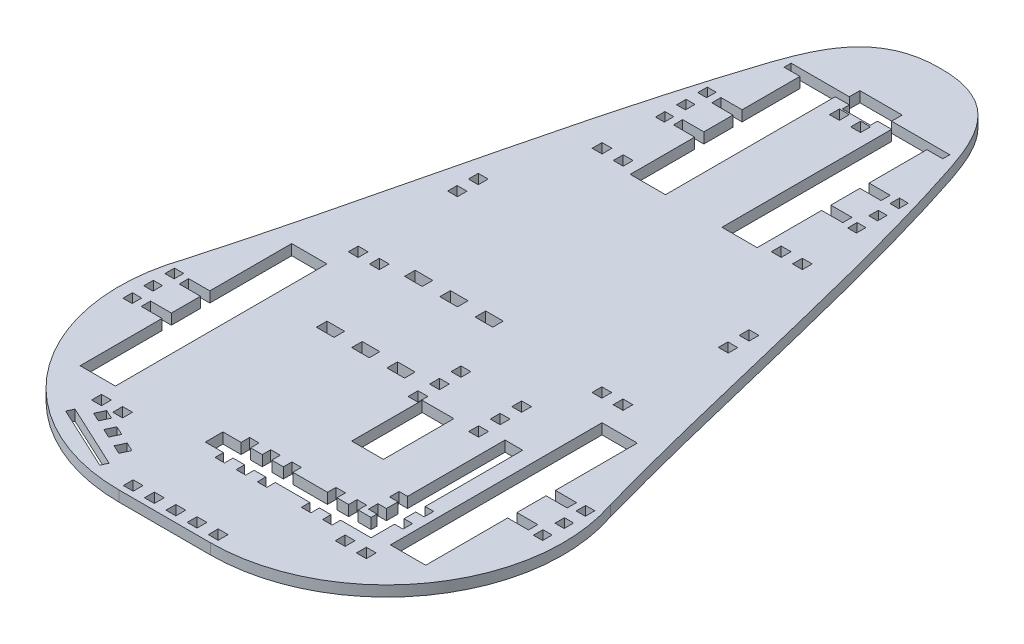
SolidWorks part; units mm, degrees
ref_plane "Front Plane" through (0, 0, 0) normal (0, 0, 1) x (1, 0, 0)
ref_plane "Top Plane" through (0, 0, 0) normal (0, 1, 0) x (1, 0, 0)
ref_plane "Right Plane" through (0, 0, 0) normal (1, 0, 0) x (0, 0, -1)
sketch "Sketch1" plane through (0, 0, 0) normal (0, 1, 0) x (1, 0, 0)
  line L0 (54.872, 210.7624) -> (54.872, -9.2376) construction
  line L1 (41.9035, -9.2376) -> (67.8405, -9.2376)
  line L6 (5.872, 75.7624) -> (15.872, 75.7624)
  line L7 (54.872, -9.2376) -> (64.872, -9.2376)
  line L8 (54.872, -9.2376) -> (44.872, -9.2376)
  line L9 (5.872, 75.7624) -> (5.872, 15.7624)
  line L10 (5.872, 15.7624) -> (15.872, 15.7624)
  line L11 (15.872, 75.7624) -> (15.872, 15.7624)
  line L12 (5.872, 75.7624) -> (15.872, 15.7624) construction
  line L13 (5.872, 15.7624) -> (15.872, 75.7624) construction
  line L18 (-0.128, 52.5374) -> (5.872, 52.5374)
  line L19 (-0.128, 52.5374) -> (-0.128, 49.8874)
  line L35 (103.872, 15.7624) -> (93.872, 15.7624)
  line L36 (93.872, 75.7624) -> (93.872, 15.7624)
  line L37 (103.872, 75.7624) -> (93.872, 75.7624)
  line L38 (103.872, 75.7624) -> (103.872, 15.7624)
  line L40 (36.872, 190.7624) -> (46.872, 190.7624)
  line L41 (36.872, 190.7624) -> (36.872, 140.7624)
  line L42 (36.872, 140.7624) -> (46.872, 140.7624)
  line L43 (46.872, 190.7624) -> (46.872, 140.7624)
  line L44 (36.872, 190.7624) -> (46.872, 140.7624) construction
  line L45 (36.872, 140.7624) -> (46.872, 190.7624) construction
  line L46 (10.872, 45.7624) -> (-10.2667, 45.7624) construction
  line L63 (72.872, 140.7624) -> (62.872, 140.7624)
  line L64 (62.872, 190.7624) -> (62.872, 140.7624)
  line L65 (72.872, 190.7624) -> (62.872, 190.7624)
  line L66 (72.872, 190.7624) -> (72.872, 140.7624)
  line L78 (114.472, 47.1124) -> (111.872, 44.4124) construction
  line L79 (114.472, 44.4124) -> (111.872, 47.1124) construction
  line L80 (114.472, 50.4124) -> (111.872, 53.1124) construction
  line L81 (114.472, 53.1124) -> (111.872, 50.4124) construction
  line L82 (109.7728, 38.9874) -> (103.7728, 41.6374) construction
  line L83 (109.7728, 41.6374) -> (103.7728, 38.9874) construction
  line L84 (109.872, 49.8874) -> (103.872, 52.5374) construction
  line L85 (109.872, 52.5374) -> (103.872, 49.8874) construction
  line L86 (111.7728, 41.1124) -> (111.7728, 38.4124)
  line L87 (114.3728, 38.4124) -> (111.7728, 38.4124)
  line L88 (114.3728, 41.1124) -> (114.3728, 38.4124)
  line L89 (111.872, 44.4124) -> (111.872, 47.1124)
  line L90 (114.472, 47.1124) -> (111.872, 47.1124)
  line L91 (114.472, 44.4124) -> (114.472, 47.1124)
  line L92 (41.872, 165.7624) -> (24.9145, 165.7624) construction
  line L93 (30.872, 172.4874) -> (36.872, 172.4874)
  line L94 (30.872, 172.4874) -> (30.872, 169.8874)
  line L95 (30.872, 169.8874) -> (36.872, 169.8874)
  line L96 (36.872, 172.4874) -> (36.872, 169.8874)
  line L97 (30.872, 172.4874) -> (36.872, 169.8874) construction
  line L98 (30.872, 169.8874) -> (36.872, 172.4874) construction
  line L103 (26.372, 161.1124) -> (28.872, 161.1124)
  line L104 (26.372, 173.1124) -> (28.872, 173.1124)
  line L105 (30.872, 161.6374) -> (36.872, 161.6374)
  line L106 (30.872, 161.6374) -> (30.872, 159.0374)
  line L107 (30.872, 159.0374) -> (36.872, 159.0374)
  line L108 (36.872, 161.6374) -> (36.872, 159.0374)
  line L109 (30.872, 161.6374) -> (36.872, 159.0374) construction
  line L110 (30.872, 159.0374) -> (36.872, 161.6374) construction
  line L111 (26.372, 173.1124) -> (26.372, 170.4124)
  line L112 (26.372, 170.4124) -> (28.872, 170.4124)
  line L113 (28.872, 173.1124) -> (28.872, 170.4124)
  line L114 (26.372, 173.1124) -> (28.872, 170.4124) construction
  line L115 (26.372, 170.4124) -> (28.872, 173.1124) construction
  line L116 (26.372, 164.4124) -> (28.872, 164.4124)
  line L117 (26.372, 164.4124) -> (26.372, 167.1124)
  line L118 (26.372, 167.1124) -> (28.872, 167.1124)
  line L119 (28.872, 164.4124) -> (28.872, 167.1124)
  line L120 (26.372, 164.4124) -> (28.872, 167.1124) construction
  line L121 (26.372, 167.1124) -> (28.872, 164.4124) construction
  line L122 (26.372, 161.1124) -> (26.372, 158.4124)
  line L123 (26.372, 158.4124) -> (28.872, 158.4124)
  line L124 (28.872, 161.1124) -> (28.872, 158.4124)
  line L125 (83.372, 167.1124) -> (80.872, 164.4124) construction
  line L126 (83.372, 164.4124) -> (80.872, 167.1124) construction
  line L127 (83.372, 170.4124) -> (80.872, 173.1124) construction
  line L128 (83.372, 173.1124) -> (80.872, 170.4124) construction
  line L129 (78.872, 159.0374) -> (72.872, 161.6374) construction
  line L130 (78.872, 161.6374) -> (72.872, 159.0374) construction
  line L131 (78.872, 169.8874) -> (72.872, 172.4874) construction
  line L132 (78.872, 172.4874) -> (72.872, 169.8874) construction
  line L133 (80.872, 161.1124) -> (80.872, 158.4124)
  line L134 (83.372, 158.4124) -> (80.872, 158.4124)
  line L135 (83.372, 161.1124) -> (83.372, 158.4124)
  line L136 (80.872, 164.4124) -> (80.872, 167.1124)
  line L137 (83.372, 167.1124) -> (80.872, 167.1124)
  line L138 (83.372, 164.4124) -> (83.372, 167.1124)
  line L139 (83.372, 164.4124) -> (80.872, 164.4124)
  line L140 (80.872, 173.1124) -> (80.872, 170.4124)
  line L141 (83.372, 170.4124) -> (80.872, 170.4124)
  line L142 (83.372, 173.1124) -> (83.372, 170.4124)
  line L143 (72.872, 161.6374) -> (72.872, 159.0374)
  line L144 (78.872, 159.0374) -> (72.872, 159.0374)
  line L145 (78.872, 161.6374) -> (78.872, 159.0374)
  line L146 (78.872, 161.6374) -> (72.872, 161.6374)
  line L147 (83.372, 173.1124) -> (80.872, 173.1124)
  line L148 (83.372, 161.1124) -> (80.872, 161.1124)
  line L149 (72.872, 172.4874) -> (72.872, 169.8874)
  line L150 (78.872, 169.8874) -> (72.872, 169.8874)
  line L151 (78.872, 172.4874) -> (78.872, 169.8874)
  line L152 (78.872, 172.4874) -> (72.872, 172.4874)
  line L153 (-0.128, 49.8874) -> (5.872, 49.8874)
  line L154 (5.872, 52.5374) -> (5.872, 49.8874)
  line L155 (-0.128, 52.5374) -> (5.872, 49.8874) construction
  line L156 (-0.128, 49.8874) -> (5.872, 52.5374) construction
  line L157 (-4.6289, 41.1124) -> (-2.0289, 41.1124)
  line L158 (-4.728, 53.1124) -> (-2.128, 53.1124)
  line L159 (-0.0289, 41.6374) -> (5.9711, 41.6374)
  line L160 (-0.0289, 41.6374) -> (-0.0289, 38.9874)
  line L161 (-0.0289, 38.9874) -> (5.9711, 38.9874)
  line L162 (5.9711, 41.6374) -> (5.9711, 38.9874)
  line L163 (-0.0289, 41.6374) -> (5.9711, 38.9874) construction
  line L164 (-0.0289, 38.9874) -> (5.9711, 41.6374) construction
  line L165 (-4.728, 53.1124) -> (-4.728, 50.4124)
  line L166 (-4.728, 50.4124) -> (-2.128, 50.4124)
  line L167 (-2.128, 53.1124) -> (-2.128, 50.4124)
  line L168 (-4.728, 53.1124) -> (-2.128, 50.4124) construction
  line L169 (-4.728, 50.4124) -> (-2.128, 53.1124) construction
  line L170 (-4.728, 44.4124) -> (-2.128, 44.4124)
  line L171 (-4.728, 44.4124) -> (-4.728, 47.1124)
  line L172 (-4.728, 47.1124) -> (-2.128, 47.1124)
  line L173 (-2.128, 44.4124) -> (-2.128, 47.1124)
  line L174 (-4.728, 44.4124) -> (-2.128, 47.1124) construction
  line L175 (-4.728, 47.1124) -> (-2.128, 44.4124) construction
  line L176 (-4.6289, 41.1124) -> (-4.6289, 38.4124)
  line L177 (-4.6289, 38.4124) -> (-2.0289, 38.4124)
  line L178 (-2.0289, 41.1124) -> (-2.0289, 38.4124)
  line L179 (114.472, 44.4124) -> (111.872, 44.4124)
  line L180 (111.872, 53.1124) -> (111.872, 50.4124)
  line L181 (114.472, 50.4124) -> (111.872, 50.4124)
  line L182 (114.472, 53.1124) -> (114.472, 50.4124)
  line L183 (103.7728, 41.6374) -> (103.7728, 38.9874)
  line L184 (109.7728, 38.9874) -> (103.7728, 38.9874)
  line L185 (109.7728, 41.6374) -> (109.7728, 38.9874)
  line L186 (109.7728, 41.6374) -> (103.7728, 41.6374)
  line L187 (114.472, 53.1124) -> (111.872, 53.1124)
  line L188 (114.3728, 41.1124) -> (111.7728, 41.1124)
  line L189 (103.872, 52.5374) -> (103.872, 49.8874)
  line L190 (109.872, 49.8874) -> (103.872, 49.8874)
  line L191 (109.872, 52.5374) -> (109.872, 49.8874)
  line L192 (109.872, 52.5374) -> (103.872, 52.5374)
  line L193 (103.872, 45.7624) -> (5.872, 45.7624) construction
  line L200 (62.872, 55.7624) -> (71.872, 55.7624)
  line L201 (62.872, 55.7624) -> (62.872, 35.7624)
  line L202 (62.872, 35.7624) -> (71.872, 35.7624)
  line L203 (71.872, 55.7624) -> (71.872, 35.7624)
  line L204 (62.872, 55.7624) -> (71.872, 35.7624) construction
  line L205 (62.872, 35.7624) -> (71.872, 55.7624) construction
  line L211 (39.9211, 61.7172) -> (44.9211, 61.7172)
  line L213 (59.9211, 69.7172) -> (62.7211, 69.7172)
  line L214 (59.9211, 57.5172) -> (62.7211, 57.5172)
  line L215 (59.9211, 57.5172) -> (59.9211, 54.7172)
  line L216 (59.9211, 54.7172) -> (62.7211, 54.7172)
  line L217 (62.7211, 57.5172) -> (62.7211, 54.7172)
  line L218 (59.9211, 57.5172) -> (62.7211, 54.7172) construction
  line L219 (59.9211, 54.7172) -> (62.7211, 57.5172) construction
  line L220 (59.9211, 69.7172) -> (59.9211, 66.9172)
  line L221 (59.9211, 66.9172) -> (62.7211, 66.9172)
  line L222 (62.7211, 69.7172) -> (62.7211, 66.9172)
  line L223 (59.9211, 63.6172) -> (62.7211, 63.6172)
  line L224 (59.9211, 63.6172) -> (59.9211, 60.8172)
  line L225 (59.9211, 60.8172) -> (62.7211, 60.8172)
  line L226 (62.7211, 63.6172) -> (62.7211, 60.8172)
  line L227 (77.1211, 69.7172) -> (79.9211, 69.7172)
  line L228 (77.1211, 57.5172) -> (79.9211, 57.5172)
  line L229 (77.1211, 57.5172) -> (77.1211, 54.7172)
  line L230 (77.1211, 54.7172) -> (79.9211, 54.7172)
  line L231 (79.9211, 57.5172) -> (79.9211, 54.7172)
  line L232 (77.1211, 69.7172) -> (77.1211, 66.9172)
  line L233 (77.1211, 66.9172) -> (79.9211, 66.9172)
  line L234 (79.9211, 69.7172) -> (79.9211, 66.9172)
  line L235 (77.1211, 63.6172) -> (79.9211, 63.6172)
  line L236 (77.1211, 63.6172) -> (77.1211, 60.8172)
  line L237 (77.1211, 60.8172) -> (79.9211, 60.8172)
  line L238 (79.9211, 63.6172) -> (79.9211, 60.8172)
  line L244 (49.9211, 61.7172) -> (54.9211, 61.7172)
  line L245 (49.9211, 61.7172) -> (49.9211, 58.7172)
  line L246 (49.9211, 58.7172) -> (54.9211, 58.7172)
  line L247 (54.9211, 61.7172) -> (54.9211, 58.7172)
  line L248 (49.9211, 61.7172) -> (54.9211, 58.7172) construction
  line L249 (49.9211, 58.7172) -> (54.9211, 61.7172) construction
  line L250 (39.9211, 61.7172) -> (39.9211, 58.7172)
  line L251 (39.9211, 58.7172) -> (44.9211, 58.7172)
  line L252 (44.9211, 61.7172) -> (44.9211, 58.7172)
  line L253 (29.9211, 61.7172) -> (34.9211, 61.7172)
  line L254 (29.9211, 61.7172) -> (29.9211, 58.7172)
  line L255 (29.9211, 58.7172) -> (34.9211, 58.7172)
  line L256 (34.9211, 61.7172) -> (34.9211, 58.7172)
  line L257 (49.9211, 86.7172) -> (54.9211, 86.7172)
  line L258 (49.9211, 86.7172) -> (49.9211, 83.7172)
  line L259 (49.9211, 83.7172) -> (54.9211, 83.7172)
  line L260 (54.9211, 86.7172) -> (54.9211, 83.7172)
  line L261 (39.9211, 86.7172) -> (44.9211, 86.7172)
  line L262 (39.9211, 86.7172) -> (39.9211, 83.7172)
  line L263 (39.9211, 83.7172) -> (44.9211, 83.7172)
  line L264 (44.9211, 86.7172) -> (44.9211, 83.7172)
  line L265 (29.9211, 86.7172) -> (34.9211, 86.7172)
  line L266 (29.9211, 86.7172) -> (29.9211, 83.7172)
  line L267 (29.9211, 83.7172) -> (34.9211, 83.7172)
  line L268 (34.9211, 86.7172) -> (34.9211, 83.7172)
  line L279 (15.072, 113.4624) -> (17.872, 113.4624)
  line L284 (15.0729, 119.4624) -> (17.8729, 119.4624)
  line L285 (15.0729, 119.4624) -> (15.0729, 116.6624)
  line L286 (15.0729, 116.6624) -> (17.8729, 116.6624)
  line L287 (17.8729, 119.4624) -> (17.8729, 116.6624)
  line L288 (15.072, 113.4624) -> (15.072, 110.7624)
  line L289 (15.072, 110.7624) -> (17.872, 110.7624)
  line L290 (17.872, 113.4624) -> (17.872, 110.7624)
  line L291 (287.5426, 108.3221) -> (290.3426, 108.3221)
  line L292 (212.3426, 111.3221) -> (290.3426, 111.3221)
  line L293 (212.3426, 111.3221) -> (212.3426, 29.7221)
  line L294 (212.3426, 29.7221) -> (290.3426, 29.7221)
  line L295 (290.3426, 111.3221) -> (290.3426, 29.7221)
  line L296 (212.3426, 108.3221) -> (215.1426, 108.3221)
  line L297 (212.3426, 108.3221) -> (212.3426, 105.5221)
  line L298 (212.3426, 105.5221) -> (215.1426, 105.5221)
  line L299 (215.1426, 108.3221) -> (215.1426, 105.5221)
  line L300 (287.5426, 108.3221) -> (287.5426, 105.5221)
  line L301 (287.5426, 105.5221) -> (290.3426, 105.5221)
  line L302 (290.3426, 108.3221) -> (290.3426, 105.5221)
  line L303 (218.3426, 108.3221) -> (221.1426, 108.3221)
  line L304 (218.3426, 108.3221) -> (218.3426, 105.5221)
  line L305 (218.3426, 105.5221) -> (221.1426, 105.5221)
  line L306 (221.1426, 108.3221) -> (221.1426, 105.5221)
  line L307 (281.5426, 84.5298) -> (284.3426, 84.5298)
  line L308 (281.5426, 84.5298) -> (281.5426, 81.7298)
  line L309 (281.5426, 81.7298) -> (284.3426, 81.7298)
  line L310 (284.3426, 84.5298) -> (284.3426, 81.7298)
  line L311 (287.5426, 35.5221) -> (290.3426, 35.5221)
  line L312 (212.3426, 35.5221) -> (215.1426, 35.5221)
  line L313 (212.3426, 35.5221) -> (212.3426, 32.7221)
  line L314 (212.3426, 32.7221) -> (215.1426, 32.7221)
  line L315 (215.1426, 35.5221) -> (215.1426, 32.7221)
  line L316 (287.5426, 35.5221) -> (287.5426, 32.7221)
  line L317 (287.5426, 32.7221) -> (290.3426, 32.7221)
  line L318 (290.3426, 35.5221) -> (290.3426, 32.7221)
  line L319 (218.3426, 35.5221) -> (221.1426, 35.5221)
  line L320 (218.3426, 35.5221) -> (218.3426, 32.7221)
  line L321 (218.3426, 32.7221) -> (221.1426, 32.7221)
  line L322 (221.1426, 35.5221) -> (221.1426, 32.7221)
  line L323 (281.5426, 35.5221) -> (284.3426, 35.5221)
  line L324 (281.5426, 35.5221) -> (281.5426, 32.7221)
  line L325 (281.5426, 32.7221) -> (284.3426, 32.7221)
  line L326 (284.3426, 35.5221) -> (284.3426, 32.7221)
  line L332 (15.9201, 84.5624) -> (18.7201, 84.5624)
  line L333 (15.9201, 84.5624) -> (15.9201, 81.7624)
  line L334 (15.9201, 81.7624) -> (18.7201, 81.7624)
  line L335 (18.7201, 84.5624) -> (18.7201, 81.7624)
  line L339 (21.9201, 84.5624) -> (24.7201, 84.5624)
  line L340 (21.9201, 84.5624) -> (21.9201, 81.7624)
  line L341 (21.9201, 81.7624) -> (24.7201, 81.7624)
  line L342 (24.7201, 84.5624) -> (24.7201, 81.7624)
  line L348 (15.9201, 11.7624) -> (18.7201, 11.7624)
  line L349 (15.9201, 11.7624) -> (15.9201, 8.9624)
  line L350 (15.9201, 8.9624) -> (18.7201, 8.9624)
  line L351 (18.7201, 11.7624) -> (18.7201, 8.9624)
  line L355 (21.9201, 11.7624) -> (24.7201, 11.7624)
  line L356 (21.9201, 11.7624) -> (21.9201, 8.9624)
  line L357 (21.9201, 8.9624) -> (24.7201, 8.9624)
  line L358 (24.7201, 11.7624) -> (24.7201, 8.9624)
  line L363 (25.072, 144.5629) -> (27.872, 144.5629)
  line L368 (25.072, 144.5629) -> (25.072, 141.7629)
  line L369 (25.072, 141.7629) -> (27.872, 141.7629)
  line L370 (27.872, 144.5629) -> (27.872, 141.7629)
  line L371 (31.072, 144.5624) -> (33.872, 144.5624)
  line L372 (31.072, 144.5624) -> (31.072, 141.7624)
  line L373 (31.072, 141.7624) -> (33.872, 141.7624)
  line L374 (33.872, 144.5624) -> (33.872, 141.7624)
  line L375 (75.872, 144.5624) -> (75.872, 141.7624)
  line L376 (78.672, 141.7624) -> (75.872, 141.7624)
  line L377 (78.672, 144.5624) -> (78.672, 141.7624)
  line L378 (78.672, 144.5624) -> (75.872, 144.5624)
  line L379 (81.872, 144.5629) -> (81.872, 141.7629)
  line L380 (84.672, 141.7629) -> (81.872, 141.7629)
  line L381 (84.672, 144.5629) -> (84.672, 141.7629)
  line L382 (84.672, 144.5629) -> (81.872, 144.5629)
  line L383 (50.4739, 186.4794) -> (50.472, 183.6794)
  line L384 (32.372, 190.884) -> (77.372, 190.884)
  line L385 (32.372, 190.884) -> (32.372, 188.884)
  line L386 (32.372, 188.884) -> (77.372, 188.884)
  line L387 (77.372, 190.884) -> (77.372, 188.884)
  line L388 (48.872, 193.884) -> (60.872, 193.884)
  line L389 (48.872, 193.884) -> (48.872, 190.884)
  line L390 (48.872, 190.884) -> (60.872, 190.884)
  line L391 (60.872, 193.884) -> (60.872, 190.884)
  line L392 (53.272, 183.6794) -> (50.472, 183.6794)
  line L393 (53.272, 186.4794) -> (53.272, 183.6794)
  line L394 (53.272, 186.4794) -> (50.4739, 186.4794)
  line L404 (85.372, 55.7624) -> (88.372, 55.7624)
  line L405 (85.372, 55.7624) -> (85.372, 15.7624)
  line L406 (85.372, 15.7624) -> (88.372, 15.7624)
  line L407 (88.372, 55.7624) -> (88.372, 15.7624)
  line L408 (44.372, 18.7624) -> (88.372, 18.7624)
  line L409 (44.372, 18.7624) -> (44.372, 15.7624)
  line L410 (44.372, 15.7624) -> (88.372, 15.7624)
  line L411 (88.372, 18.7624) -> (88.372, 15.7624)
  line L471 (41.9035, -9.2376) -> (64.872, -9.2376)
  line L480 (47.522, 22.1624) -> (47.522, 19.7624)
  line L481 (50.222, 19.7624) -> (47.522, 19.7624)
  line L482 (50.222, 22.1624) -> (50.222, 19.7624)
  line L483 (50.222, 22.1624) -> (47.522, 22.1624)
  line L484 (53.522, 22.1624) -> (53.522, 19.7624)
  line L485 (56.222, 19.7624) -> (53.522, 19.7624)
  line L486 (56.222, 22.1624) -> (56.222, 19.7624)
  line L487 (56.222, 22.1624) -> (53.522, 22.1624)
  line L488 (59.522, 22.1624) -> (59.522, 19.7624)
  line L489 (62.222, 19.7624) -> (59.522, 19.7624)
  line L490 (62.222, 22.1624) -> (62.222, 19.7624)
  line L491 (62.222, 22.1624) -> (59.522, 22.1624)
  line L492 (56.472, 186.4794) -> (59.2701, 186.4794)
  line L493 (56.472, 186.4794) -> (56.472, 183.6794)
  line L494 (56.472, 183.6794) -> (59.272, 183.6794)
  line L495 (59.2701, 186.4794) -> (59.272, 183.6794)
  line L496 (94.672, 113.4624) -> (94.672, 110.7624)
  line L497 (94.672, 110.7624) -> (91.872, 110.7624)
  line L498 (91.872, 113.4624) -> (91.872, 110.7624)
  line L499 (94.672, 113.4624) -> (91.872, 113.4624)
  line L500 (94.671, 119.4624) -> (94.671, 116.6624)
  line L501 (94.671, 116.6624) -> (91.871, 116.6624)
  line L502 (91.871, 119.4624) -> (91.871, 116.6624)
  line L503 (94.671, 119.4624) -> (91.871, 119.4624)
  line L504 (87.8238, 11.7624) -> (87.8238, 8.9624)
  line L505 (87.8238, 8.9624) -> (85.0238, 8.9624)
  line L506 (85.0238, 11.7624) -> (85.0238, 8.9624)
  line L507 (87.8238, 11.7624) -> (85.0238, 11.7624)
  line L508 (93.8238, 11.7624) -> (93.8238, 8.9624)
  line L509 (93.8238, 8.9624) -> (91.0238, 8.9624)
  line L510 (91.0238, 11.7624) -> (91.0238, 8.9624)
  line L511 (93.8238, 11.7624) -> (91.0238, 11.7624)
  line L512 (87.8238, 84.5624) -> (87.8238, 81.7624)
  line L513 (87.8238, 81.7624) -> (85.0238, 81.7624)
  line L514 (85.0238, 84.5624) -> (85.0238, 81.7624)
  line L515 (87.8238, 84.5624) -> (85.0238, 84.5624)
  line L516 (93.8238, 84.5624) -> (93.8238, 81.7624)
  line L517 (93.8238, 81.7624) -> (91.0238, 81.7624)
  line L518 (91.0238, 84.5624) -> (91.0238, 81.7624)
  line L519 (93.8238, 84.5624) -> (91.0238, 84.5624)
  line L520 (76.372, 18.7624) -> (76.372, 15.7624) construction
  line L521 (64.372, 18.7624) -> (88.372, 18.7624)
  line L522 (64.372, 18.7624) -> (64.372, 15.7624)
  line L523 (64.372, 15.7624) -> (88.372, 15.7624)
  line L524 (88.372, 18.7624) -> (88.372, 15.7624)
  line L525 (76.372, 27.5136) -> (76.372, 8.1564) construction
  line L526 (85.372, 25.7624) -> (88.372, 25.7624) construction
  line L527 (85.372, 35.7624) -> (88.372, 35.7624)
  line L528 (85.372, 35.7624) -> (85.372, 15.7624)
  line L529 (85.372, 15.7624) -> (88.372, 15.7624)
  line L530 (88.372, 35.7624) -> (88.372, 15.7624)
  line L531 (91.4767, 25.7624) -> (69.6189, 25.7624) construction
  line L532 (44.372, 17.2624) -> (64.372, 17.2624) construction
  line L537 (84.372, 57.7624) -> (89.372, 57.7624)
  line L538 (84.372, 57.7624) -> (84.372, 14.7624)
  line L539 (84.372, 14.7624) -> (89.372, 14.7624)
  line L540 (89.372, 57.7624) -> (89.372, 14.7624)
  line L541 (42.372, 19.7624) -> (89.372, 19.7624)
  line L542 (42.372, 19.7624) -> (42.372, 14.7624)
  line L543 (42.372, 14.7624) -> (89.372, 14.7624)
  line L544 (89.372, 19.7624) -> (89.372, 14.7624)
  line L545 (74.722, 14.7624) -> (74.722, 12.3624)
  line L546 (74.722, 12.3624) -> (72.022, 12.3624)
  line L547 (72.022, 14.7624) -> (72.022, 12.3624)
  line L548 (74.722, 14.7624) -> (72.022, 14.7624)
  line L553 (80.722, 14.7624) -> (80.722, 12.3624)
  line L554 (78.022, 14.7624) -> (80.722, 14.7624)
  line L555 (78.022, 14.7624) -> (78.022, 12.3624)
  line L556 (78.022, 12.3624) -> (80.722, 12.3624)
  line L557 (64.372, 17.2624) -> (88.372, 17.2624) construction
  line L558 (78.022, 19.7624) -> (80.722, 19.7624)
  line L559 (78.022, 19.7624) -> (78.022, 22.1624)
  line L560 (78.022, 22.1624) -> (80.722, 22.1624)
  line L561 (80.722, 19.7624) -> (80.722, 22.1624)
  line L562 (72.022, 19.7624) -> (72.022, 22.1624)
  line L563 (74.722, 19.7624) -> (72.022, 19.7624)
  line L564 (74.722, 19.7624) -> (74.722, 22.1624)
  line L565 (74.722, 22.1624) -> (72.022, 22.1624)
  line L566 (81.972, 27.4124) -> (84.372, 27.4124)
  line L567 (81.972, 27.4124) -> (81.972, 30.1124)
  line L568 (81.972, 30.1124) -> (84.372, 30.1124)
  line L569 (84.372, 27.4124) -> (84.372, 30.1124)
  line L574 (86.872, 35.7624) -> (86.872, 15.7624) construction
  line L575 (81.972, 24.1124) -> (81.972, 21.4124)
  line L576 (81.972, 21.4124) -> (84.372, 21.4124)
  line L577 (84.372, 24.1124) -> (84.372, 21.4124)
  line L578 (81.972, 24.1124) -> (84.372, 24.1124)
  line L579 (91.772, 24.1124) -> (89.372, 24.1124)
  line L580 (89.372, 24.1124) -> (89.372, 21.4124)
  line L581 (91.772, 21.4124) -> (89.372, 21.4124)
  line L582 (91.772, 24.1124) -> (91.772, 21.4124)
  line L583 (91.772, 27.4124) -> (91.772, 30.1124)
  line L584 (91.772, 30.1124) -> (89.372, 30.1124)
  line L585 (89.372, 27.4124) -> (89.372, 30.1124)
  line L586 (91.772, 27.4124) -> (89.372, 27.4124)
  line L588 (50.872, 188.884) -> (58.872, 188.884)
  line L589 (50.872, 188.884) -> (50.872, 186.884)
  line L590 (50.872, 186.884) -> (58.872, 186.884)
  line L591 (58.872, 188.884) -> (58.872, 186.884)
  line L659 (24.863, 0.1599) -> (24.0178, -1.6527) construction
  line L660 (59.522, -4.7376) -> (62.322, -4.7376)
  line L661 (53.522, -4.7376) -> (56.322, -4.7376)
  line L662 (53.522, -4.7376) -> (53.522, -7.5376)
  line L663 (53.522, -7.5376) -> (56.322, -7.5376)
  line L664 (56.322, -4.7376) -> (56.322, -7.5376)
  line L665 (59.522, -4.7376) -> (59.522, -7.5376)
  line L666 (59.522, -7.5376) -> (62.322, -7.5376)
  line L667 (62.322, -4.7376) -> (62.322, -7.5376)
  line L668 (65.522, -4.7376) -> (68.322, -4.7376)
  line L669 (65.522, -4.7376) -> (65.522, -7.5376)
  line L670 (65.522, -7.5376) -> (68.322, -7.5376)
  line L671 (68.322, -4.7376) -> (68.322, -7.5376)
  line L672 (44.222, -4.7376) -> (44.222, -7.5376)
  line L673 (44.222, -7.5376) -> (41.422, -7.5376)
  line L674 (41.422, -4.7376) -> (41.422, -7.5376)
  line L675 (44.222, -4.7376) -> (41.422, -4.7376)
  line L676 (50.222, -4.7376) -> (50.222, -7.5376)
  line L677 (50.222, -7.5376) -> (47.422, -7.5376)
  line L678 (47.422, -4.7376) -> (47.422, -7.5376)
  line L679 (50.222, -4.7376) -> (47.422, -4.7376)
  line L689 (20.6529, 8.5227) -> (19.4695, 5.9851)
  line L690 (22.0072, 4.8017) -> (19.4695, 5.9851)
  line L691 (14.9547, 2.5735) -> (33.0809, -5.8789)
  line L692 (14.9547, 2.5735) -> (15.8, 4.3861)
  line L693 (15.8, 4.3861) -> (33.9261, -4.0663)
  line L694 (33.0809, -5.8789) -> (33.9261, -4.0663)
  line L698 (23.1905, 7.3394) -> (22.0072, 4.8017)
  line L699 (23.1905, 7.3394) -> (20.6529, 8.5227)
  line L700 (26.0907, 5.987) -> (24.9074, 3.4493)
  line L701 (27.445, 2.266) -> (24.9074, 3.4493)
  line L702 (28.6284, 4.8037) -> (27.445, 2.266)
  line L703 (28.6284, 4.8037) -> (26.0907, 5.987)
  line L704 (31.5286, 3.4513) -> (30.3452, 0.9136)
  line L705 (32.8829, -0.2697) -> (30.3452, 0.9136)
  line L706 (34.0662, 2.268) -> (32.8829, -0.2697)
  line L707 (34.0662, 2.268) -> (31.5286, 3.4513)
  line L708 (62.222, 12.3624) -> (59.522, 12.3624)
  line L709 (62.222, 12.3624) -> (62.222, 14.7624)
  line L710 (62.222, 14.7624) -> (59.522, 14.7624)
  line L711 (59.522, 12.3624) -> (59.522, 14.7624)
  line L712 (56.222, 12.3624) -> (53.522, 12.3624)
  line L713 (56.222, 12.3624) -> (56.222, 14.7624)
  line L714 (56.222, 14.7624) -> (53.522, 14.7624)
  line L715 (53.522, 12.3624) -> (53.522, 14.7624)
  line L716 (50.222, 12.3624) -> (47.522, 12.3624)
  line L717 (50.222, 12.3624) -> (50.222, 14.7624)
  line L718 (50.222, 14.7624) -> (47.522, 14.7624)
  line L719 (47.522, 12.3624) -> (47.522, 14.7624)
  arc A0 (41.9035, -9.2376) -> (-5.452, 56.8081) centre (41.9035, 40.7624) cw
  arc A1 (67.8405, -9.2376) -> (115.1959, 56.8081) centre (67.8405, 40.7624) ccw
  spline S0 degree 3 poles (54.872, 210.7624) (53.982, 210.7624) (36.6831, 210.353) (26.6517, 181.7608) (12.4717, 130.3178) (2.6705, 85.557) (-5.452, 56.8081) knots 0 0 0 0 0.011072 0.22144 0.460221 1 1 1 1
  spline S1 degree 3 poles (54.872, 210.7624) (55.7619, 210.7624) (73.0609, 210.353) (83.0922, 181.7608) (97.2722, 130.3178) (107.0734, 85.557) (115.1959, 56.8081) knots 0 0 0 0 0.011072 0.22144 0.460221 1 1 1 1
  point P4 (2.872, 51.2124)
  point P24 (10.872, 45.7624)
  point P30 (-3.428, 51.7624)
  point P33 (2.9711, 40.3124)
  point P40 (-3.428, 45.7624)
  point P50 (41.872, 165.7624)
  point P67 (33.872, 171.1874)
  point P82 (27.622, 171.7624)
  point P85 (33.872, 160.3374)
  point P92 (27.622, 165.7624)
  point P121 (82.122, 165.7624)
  point P122 (75.872, 160.3374)
  point P123 (82.122, 171.7624)
  point P124 (75.872, 171.1874)
  point P131 (113.172, 45.7624)
  point P132 (106.7728, 40.3124)
  point P133 (113.172, 51.7624)
  point P134 (106.872, 51.2124)
  point P141 (67.372, 45.7624)
  point P151 (61.3211, 56.1172)
  point P177 (52.4211, 60.2172)
  point P370 (24.4404, -0.7464)
  dimension "D6" = 10
  dimension "D7" = 50
  dimension "D10" = 6
  dimension "D2" = 173.1277
  dimension "D1" = 220
  dimension "D3" = 60.3239
  dimension "D4" = 10
  dimension "D5" = 10
  dimension "D8" = 60
  dimension "D9" = 6
  dimension "D11" = 25
  dimension "D12" = 2.6
  dimension "D13" = 2.7
  dimension "D14" = 2.6
  dimension "D15" = 2.7
  dimension "D16" = 2
  dimension "D17" = 2
  dimension "D18" = 39
  dimension "D19" = 2.6
  dimension "D20" = 10
  dimension "D21" = 50
  dimension "D22" = 20
  dimension "D23" = 8
  dimension "D24" = 8.25
  dimension "D25" = 0
  dimension "D26" = 0
  dimension "D27" = 3.3
  dimension "D28" = 3.3
  dimension "D29" = 8.25
  dimension "D30" = 4.125
  dimension "D31" = 2.5
  dimension "D32" = 2.7
  dimension "D33" = 2.7
  dimension "D34" = 6
  dimension "D35" = 2.6
  dimension "D36" = 8.25
  dimension "D37" = 4.125
  dimension "D38" = 2.6
  dimension "D39" = 6
  dimension "D40" = 0
  dimension "D41" = 0
  dimension "D42" = 2.5
  dimension "D43" = 2.7
  dimension "D44" = 2.5
  dimension "D45" = 2.7
  dimension "D46" = 2
  dimension "D47" = 2
  dimension "D48" = 3.3
  dimension "D49" = 2.5
  dimension "D50" = 2.7
  dimension "D51" = 3
  dimension "0.33" = 3.3
  dimension "D52" = 2
  dimension "D53" = 52
  dimension "D54" = 2
  dimension "D55" = 2.65
  dimension "D56" = 2.8
  dimension "D57" = 9
  dimension "D58" = 20
  dimension "D59" = 10
  dimension "D60" = 47
  dimension "D61" = 24
  dimension "D62" = 0
  dimension "D63" = 2.8
  dimension "D64" = 2.8
  dimension "D65" = 0
  dimension "D66" = 5
  dimension "D67" = 3
  dimension "D68" = 3
  dimension "D69" = 20
  dimension "D70" = 3.3
  dimension "D71" = 2.8
  dimension "D72" = 2.8
  dimension "D73" = 3.3
  dimension "D74" = 2.8
  dimension "D75" = 2.8
  dimension "D76" = 2.8
  dimension "D77" = 2.8
  dimension "D78" = 2.8
  dimension "D79" = 2.8
  dimension "D80" = 3.3
  dimension "D81" = 3.3
  dimension "D82" = 0
  dimension "D83" = 5
  dimension "D84" = 3
  dimension "D85" = 5
  dimension "D86" = 0
  dimension "D87" = 5
  dimension "D88" = 5
  dimension "D89" = 3
  dimension "D90" = 5
  dimension "D91" = 3
  dimension "D92" = 2.8
  dimension "D93" = 2.8
  dimension "D94" = 5
  dimension "D95" = 3
  dimension "D96" = 2.7
  dimension "D97" = 5
  dimension "D98" = 5
  dimension "D99" = 3
  dimension "D100" = 2.8
  dimension "D101" = 5
  dimension "D102" = 3.2
  dimension "D103" = 0.001
  dimension "D104" = 37
  dimension "D105" = 30
  dimension "D106" = 78
  dimension "D107" = 81.6
  dimension "D108" = 2.8
  dimension "D109" = 2.8
  dimension "D110" = 3
  dimension "D111" = 0
  dimension "D112" = 2.8
  dimension "D113" = 2.8
  dimension "D114" = 3
  dimension "D115" = 3.2
  dimension "D116" = 2.8
  dimension "D117" = 2.8
  dimension "D118" = 2.8
  dimension "D119" = 0
  dimension "D120" = 2.8
  dimension "D121" = 2.8
  dimension "D122" = 2.8
  dimension "D123" = 3.2
  dimension "D124" = 3.2
  dimension "D125" = 2.8
  dimension "D126" = 2.8
  dimension "D127" = 2.8
  dimension "D128" = 2.8
  dimension "D129" = 3.2
  dimension "D130" = 2.8
  dimension "D131" = 2.8
  dimension "D132" = 0
  dimension "D133" = 0
  dimension "D134" = 3
  dimension "D135" = 3
  dimension "D136" = 70
  dimension "D137" = 2.8
  dimension "0.28" = 2.8
  dimension "D139" = 2.8
  dimension "D140" = 2.8
  dimension "D141" = 2.8
  dimension "D142" = 2.8
  dimension "D143" = 3.2
  dimension "D144" = 3.2
  dimension "D145" = 2
  dimension "D146" = 2.8
  dimension "D147" = 5
  dimension "D148" = 43
  dimension "D149" = 5
  dimension "D150" = 3.2
  dimension "D151" = 1
  dimension "D152" = 2.8
  dimension "D153" = 2.8
  dimension "D154" = 3.2
  dimension "D155" = 2.8
  dimension "D156" = 2.8
  dimension "D157" = 47
  dimension "D158" = 12.5
  dimension "D159" = 4.5
  dimension "D160" = 18
  dimension "D161" = 2.5
  dimension "D162" = 3
  dimension "D163" = 45
  dimension "D164" = 2
  dimension "D165" = 22.5
  dimension "D166" = 70
  dimension "D167" = 12
  dimension "D168" = 3
  dimension "D169" = 0
  dimension "D170" = 6
  dimension "D171" = 2.8
  dimension "D172" = 2.8
  dimension "D173" = 0
  dimension "D174" = 0
  dimension "D175" = 0
  dimension "D176" = 1.6
  dimension "D177" = 1.7
  dimension "D178" = 2.65
  dimension "D179" = 2.4
  dimension "D180" = 2.7
  dimension "D181" = 3
  dimension "D182" = 40
  dimension "D183" = 10
  dimension "D184" = 3
  dimension "D185" = 44
  dimension "D186" = 5.5
  dimension "D187" = 0
  dimension "D188" = 0
  dimension "D189" = 2.4
  dimension "D190" = 2.7
  dimension "D191" = 1.65
  dimension "D192" = 0
  dimension "D195" = 20
  dimension "D196" = 3.2
  dimension "D197" = 2.8
  dimension "D198" = 2.8
  dimension "D199" = 2.8
  dimension "D200" = 2.8
  dimension "D201" = 0
  dimension "D202" = 4
  dimension "D203" = 2.8
  dimension "D205" = 0
  dimension "D210" = 2.7
  dimension "D211" = 2.4
  dimension "D212" = 2.7
  dimension "D213" = 2.4
  dimension "D214" = 2.7
  dimension "D215" = 2.4
  dimension "D216" = 1.35
  dimension "D217" = 2.4
  dimension "D218" = 2.4
  dimension "D219" = 2.4
  dimension "D220" = 2.4
  dimension "D221" = 2.7
  dimension "D222" = 2.7
  dimension "D223" = 1.65
  dimension "D224" = 0
  dimension "D225" = 2.4
  dimension "D226" = 8
  dimension "D227" = 4
  dimension "D228" = 2
  dimension "D229" = 0
  dimension "D230" = 2.8
  dimension "D231" = 2.8
  dimension "D232" = 2.8
  dimension "D233" = 2.8
  dimension "D234" = 0
  dimension "D235" = 2.8
  dimension "D236" = 3.3
  dimension "D237" = 2.7
  dimension "D238" = 2.7
  dimension "D239" = 3.3
  dimension "D240" = 180
  dimension "D241" = 1.35
  dimension "D242" = 1.35
  dimension "D243" = 3.2
  dimension "D244" = 2.8
  dimension "D245" = 3.2
  dimension "D246" = 3
  dimension "D247" = 2.8
  dimension "D248" = 2
  dimension "D249" = 46
  dimension "D250" = 30.4315
  dimension "D138" = 2.8
extrude "Boss-Extrude1" add sketch "Sketch1" along normal blind 3 contours L0 S0 A0 L1 | S1 L0 L1 A1 region at (3.3293, 0, -13.1044)
